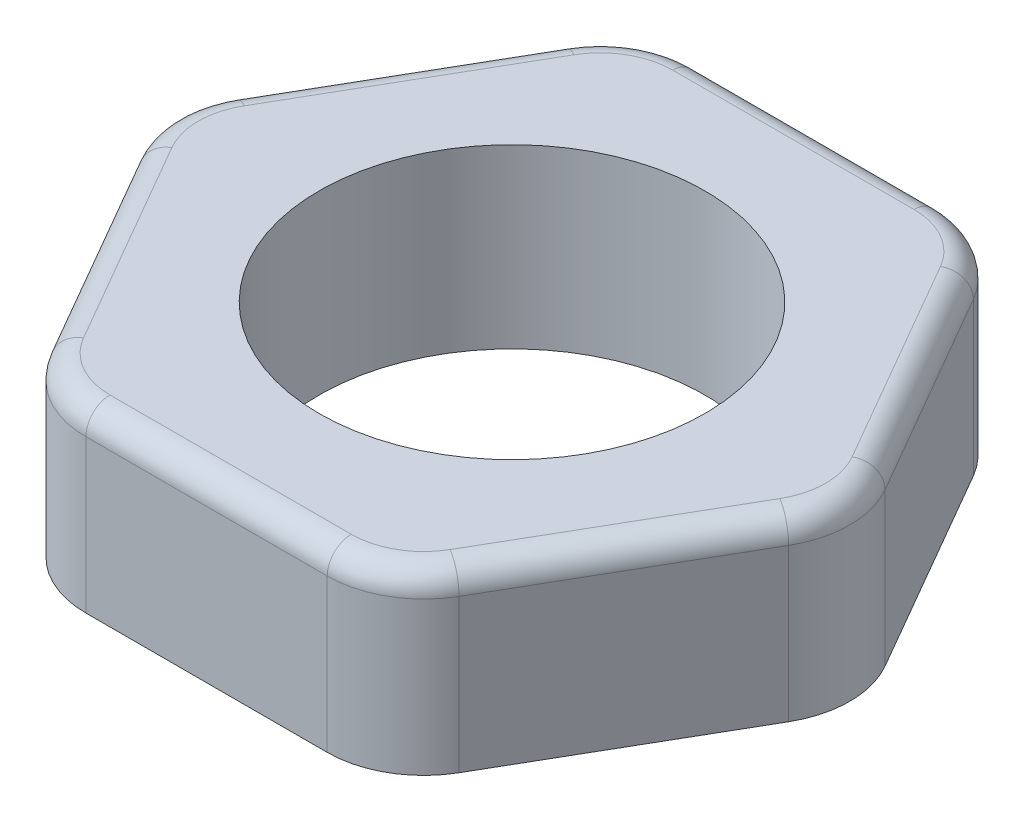
SolidWorks part; units mm, degrees
ref_plane "Front Plane" through (0, 0, 0) normal (0, 0, 1) x (1, 0, 0)
ref_plane "Top Plane" through (0, 0, 0) normal (0, 1, 0) x (1, 0, 0)
ref_plane "Right Plane" through (0, 0, 0) normal (1, 0, 0) x (0, 0, -1)
sketch "Sketch1" plane through (0, 0, 0) normal (0, 1, 0) x (1, 0, 0)
  line L1 (10.9697, 0) -> (5.4848, 9.5)
  line L2 (5.4848, 9.5) -> (-5.4848, 9.5)
  line L3 (-5.4848, 9.5) -> (-10.9697, 0)
  line L4 (-10.9697, 0) -> (-5.4848, -9.5)
  line L5 (-5.4848, -9.5) -> (5.4848, -9.5)
  line L6 (5.4848, -9.5) -> (10.9697, 0)
  circle A0 centre (0, 0) radius 9.5 construction
  dimension "D1" = 19
extrude "Boss-Extrude1" add sketch "Sketch1" along normal blind 5.5
fillet "Fillet1" radius 0.75 6 edges at (-8.2272, 5.5, 4.75) (-8.2272, 5.5, -4.75) (0, 5.5, -9.5) (8.2272, 5.5, -4.75) (8.2272, 5.5, 4.75) (0, 5.5, 9.5)
fillet "Fillet2" radius 3 12 edges at (5.358, 5.2803, 9.2803) (10.716, 5.2803, 0) (5.358, 5.2803, -9.2803) (-5.358, 5.2803, -9.2803) (-10.716, 5.2803, 0) (-5.358, 5.2803, 9.2803) (-5.4848, 2.375, 9.5) (-10.9697, 2.375, 0) (-5.4848, 2.375, -9.5) (5.4848, 2.375, -9.5) (10.9697, 2.375, 0) (5.4848, 2.375, 9.5)
sketch "Sketch2" plane through (0, 5.5, 0) normal (0, 1, 0) x (1, 0, 0)
  circle A0 centre (0, 0) radius 6
  dimension "D1" = 12
extrude "Cut-Extrude1" cut sketch "Sketch2" against normal through all
